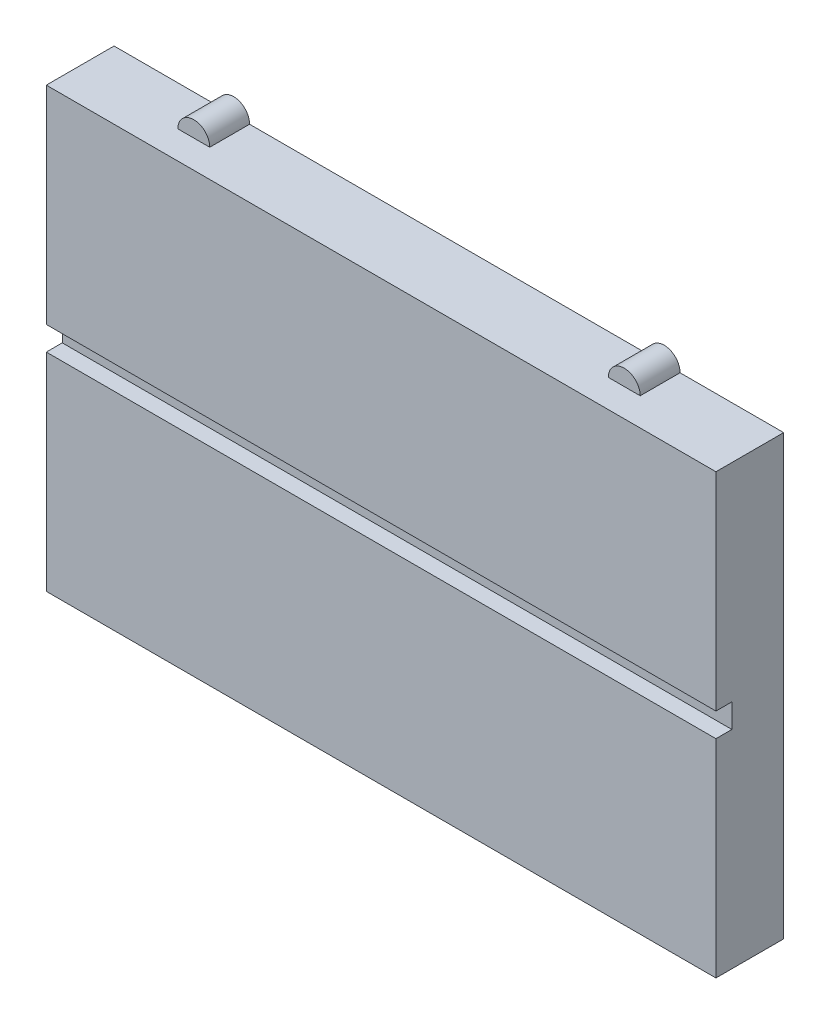
SolidWorks part; units mm, degrees
ref_plane "正面" through (0, 0, 0) normal (0, 0, 1) x (1, 0, 0)
ref_plane "平面" through (0, 0, 0) normal (0, 1, 0) x (1, 0, 0)
ref_plane "右側面" through (0, 0, 0) normal (1, 0, 0) x (0, 0, -1)
sketch "ｽｹｯﾁ1" plane through (0, 0, 0) normal (0, 0, 1) x (1, 0, 0)
  line L1 (42, -27.5) -> (-42, -27.5)
  line L2 (42, -27.5) -> (42, 27.5)
  line L3 (42, 27.5) -> (-42, 27.5)
  line L4 (-42, -27.5) -> (-42, 27.5)
  line L5 (42, -27.5) -> (-42, 27.5) construction
  line L6 (42, 27.5) -> (-42, -27.5) construction
  arc A0 (-42, 24.5) -> (-42, 20.5) centre (-42, 22.5) ccw
  arc A1 (-42, -20.5) -> (-42, -24.5) centre (-42, -22.5) ccw
  arc A4 (-25, 27.5) -> (-29, 27.5) centre (-27, 27.5) ccw
  arc A5 (29, 27.5) -> (25, 27.5) centre (27, 27.5) ccw
  arc A6 (-42, 2) -> (-42, -2) centre (-42, 0) ccw
  point P0 (0, 0)
  dimension "D3" = 4
  dimension "D1" = 84
  dimension "D2" = 55
  dimension "D4" = 5
  dimension "D5" = 5
  dimension "D6" = 15
  dimension "D7" = 15
extrude "ﾎﾞｽ - 押し出し2" add sketch "ｽｹｯﾁ1" along normal blind 8.5 contours L4 L1 L2 L3 region at (0, 0, 0)
extrude "ﾎﾞｽ - 押し出し3" add sketch "ｽｹｯﾁ1<3>" along normal blind 5 contours L3 A4 | L4 A0 | L4 A6 | L4 A1 | L3 A5 region at (-42.8488, -22.5, 0) region at (27, 28.3488, 0) region at (-42.8488, 0, 0) region at (-27, 28.3488, 0) region at (-42.8488, 22.5, 0)
sketch "ｽｹｯﾁ1<3>" plane through (0, 0, 0) normal (0, 0, 1) x (1, 0, 0) same geometry as "ｽｹｯﾁ1"
sketch "ｽｹｯﾁ2" plane through (0, 0, 8.5) normal (0, 0, 1) x (1, 0, 0)
  line L0 (-42, -27.5) -> (-42, 27.5) construction
  line L1 (42, -1.5) -> (-42, -1.5)
  line L2 (42, -1.5) -> (42, 1.5)
  line L3 (42, 1.5) -> (-42, 1.5)
  line L4 (-42, -1.5) -> (-42, 1.5)
  line L5 (42, -1.5) -> (-42, 1.5) construction
  line L6 (42, 1.5) -> (-42, -1.5) construction
  point P0 (0, 0)
  dimension "D1" = 3
extrude "ｶｯﾄ - 押し出し1" cut sketch "ｽｹｯﾁ2" against normal blind 2
